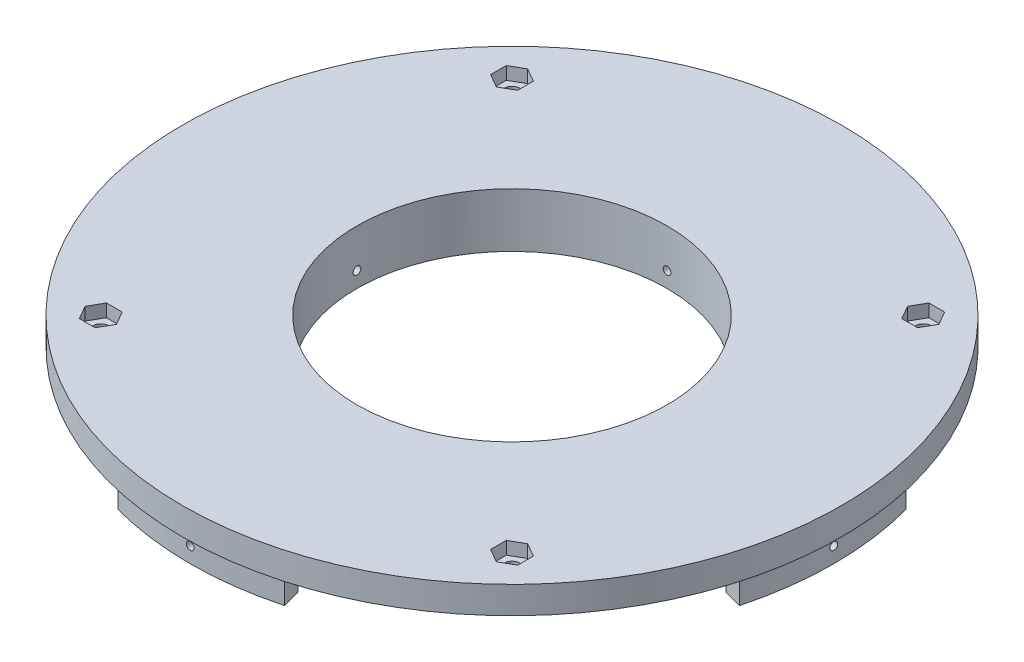
SolidWorks part; units mm, degrees
ref_plane "Front Plane" through (0, 0, 0) normal (0, 0, 1) x (1, 0, 0)
ref_plane "Top Plane" through (0, 0, 0) normal (0, 1, 0) x (1, 0, 0)
ref_plane "Right Plane" through (0, 0, 0) normal (1, 0, 0) x (0, 0, -1)
sketch "Sketch1" plane through (0, 0, 0) normal (0, 1, 0) x (1, 0, 0)
  line L0 (-85, 0) -> (85, 0) construction
  line L1 (0, 85) -> (0, -85) construction
  circle A0 centre (0, 0) radius 85
  circle A1 centre (0, 0) radius 40
  dimension "D1" = 170
  dimension "D2" = 80
extrude "Boss-Extrude1" add sketch "Sketch1" along normal blind 7
sketch "Sketch11" plane through (0, 0, 0) normal (0, -1, 0) x (1, 0, 0)
  line L1 (75.3422, 20.1879) -> (80.1718, 21.482)
  line L2 (75.3422, -20.1879) -> (80.1718, -21.482)
  line L5 (20.1879, -75.3422) -> (21.482, -80.1718)
  line L6 (-20.1879, -75.3422) -> (-21.482, -80.1718)
  line L7 (-75.3422, -20.1879) -> (-80.1718, -21.482)
  line L8 (-75.3422, 20.1879) -> (-80.1718, 21.482)
  line L9 (-20.1879, 75.3422) -> (-21.482, 80.1718)
  line L10 (20.1879, 75.3422) -> (21.482, 80.1718)
  circle A2 centre (0, 0) radius 40
  circle A3 centre (0, 0) radius 45
  arc A8 (80.1718, -21.482) -> (80.1718, 21.482) centre (0, 0) ccw
  arc A9 (75.3422, -20.1879) -> (75.3422, 20.1879) centre (0, 0) ccw
  arc A10 (-20.1879, -75.3422) -> (20.1879, -75.3422) centre (0, 0) ccw
  arc A11 (-21.482, -80.1718) -> (21.482, -80.1718) centre (0, 0) ccw
  arc A12 (-75.3422, 20.1879) -> (-75.3422, -20.1879) centre (0, 0) ccw
  arc A13 (-80.1718, 21.482) -> (-80.1718, -21.482) centre (0, 0) ccw
  arc A14 (20.1879, 75.3422) -> (-20.1879, 75.3422) centre (0, 0) ccw
  arc A15 (21.482, 80.1718) -> (-21.482, 80.1718) centre (0, 0) ccw
  point P23 (0, 0)
  dimension "D1" = 4
extrude "Boss-Extrude2" add sketch "Sketch11" along normal blind 7
sketch "Sketch13" plane through (0, 0, 0) normal (1, 0, 0) x (0, 0, -1)
  line L1 (40, 0) -> (-40, 0) construction
  circle A1 centre (0, -3) radius 1
  dimension "D1" = 3
extrude "Cut-Extrude1" cut sketch "Sketch13" against normal blind 133 and the other way blind 110
sketch "Sketch14" plane through (0, 7, 0) normal (0, 1, 0) x (1, 0, 0)
  circle A0 centre (-53.033, 53.033) radius 2
  circle A1 centre (53.033, 53.033) radius 2
  circle A2 centre (53.033, -53.033) radius 2
  circle A3 centre (-53.033, -53.033) radius 2
  point P14 (0, 0)
  dimension "D1" = 75
  dimension "D2" = 4
extrude "Cut-Extrude2" cut sketch "Sketch14" against normal blind 133
sketch "Sketch15" plane through (0, 7, 0) normal (0, 1, 0) x (1, 0, 0)
  line L0 (0, 85) -> (0, -85) construction
  line L1 (-49.533, 55.0537) -> (-53.033, 57.0745)
  line L2 (-53.033, 57.0745) -> (-56.533, 55.0537)
  line L3 (-56.533, 55.0537) -> (-56.533, 51.0123)
  line L4 (-56.533, 51.0123) -> (-53.033, 48.9916)
  line L5 (-53.033, 48.9916) -> (-49.533, 51.0123)
  line L6 (-49.533, 51.0123) -> (-49.533, 55.0537)
  line L7 (55.0537, 49.533) -> (57.0745, 53.033)
  line L8 (57.0745, 53.033) -> (55.0537, 56.533)
  line L9 (55.0537, 56.533) -> (51.0123, 56.533)
  line L10 (51.0123, 56.533) -> (48.9916, 53.033)
  line L11 (48.9916, 53.033) -> (51.0123, 49.533)
  line L12 (51.0123, 49.533) -> (55.0537, 49.533)
  line L13 (49.533, -55.0537) -> (53.033, -57.0745)
  line L14 (53.033, -57.0745) -> (56.533, -55.0537)
  line L15 (56.533, -55.0537) -> (56.533, -51.0123)
  line L16 (56.533, -51.0123) -> (53.033, -48.9916)
  line L17 (53.033, -48.9916) -> (49.533, -51.0123)
  line L18 (49.533, -51.0123) -> (49.533, -55.0537)
  line L19 (-55.0537, -49.533) -> (-57.0745, -53.033)
  line L20 (-57.0745, -53.033) -> (-55.0537, -56.533)
  line L21 (-55.0537, -56.533) -> (-51.0123, -56.533)
  line L22 (-51.0123, -56.533) -> (-48.9916, -53.033)
  line L23 (-48.9916, -53.033) -> (-51.0123, -49.533)
  line L24 (-51.0123, -49.533) -> (-55.0537, -49.533)
  circle A0 centre (-53.033, 53.033) radius 3.5 construction
  point P32 (0, 0)
  dimension "D1" = 7
  dimension "D2" = 4
extrude "Cut-Extrude3" cut sketch "Sketch15" against normal blind 3.3
pattern_circular "CirPattern1" count 2 every 90 about axis through (0, 7, 0) along (0, 1, 0) of "Cut-Extrude1"
